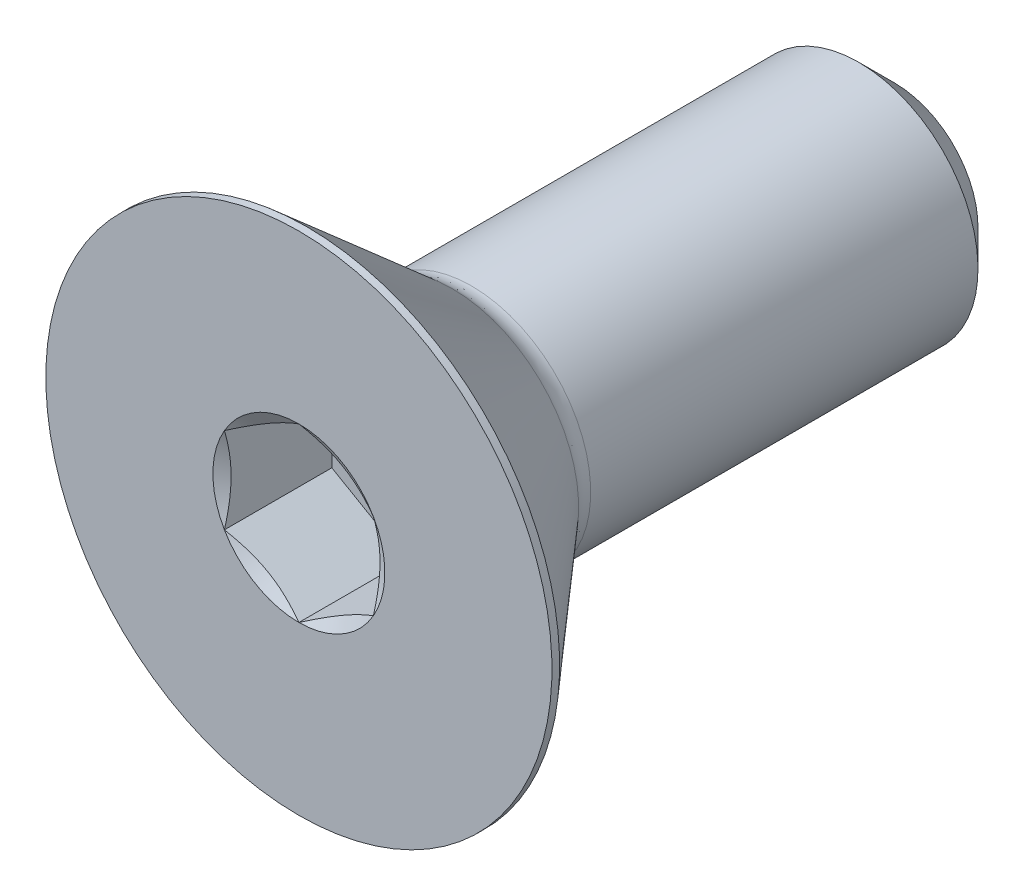
SolidWorks part; units mm, degrees
ref_plane "Front" through (0, 0, 0) normal (0, 0, 1) x (1, 0, 0)
ref_plane "Top" through (0, 0, 0) normal (0, 1, 0) x (1, 0, 0)
ref_plane "Right" through (0, 0, 0) normal (1, 0, 0) x (0, 0, -1)
sketch "Sketch1" plane through (0, 0, 0) normal (1, 0, 0) x (0, 0, -1)
  line L0 (0, 6.7437) -> (0.2045, 6.7437) construction
  line L1 (0.2045, 6.7437) -> (4.0894, 3.3666) construction
  line L2 (0, 3.175) -> (15.875, 3.175)
  line L3 (15.875, 3.175) -> (15.875, 0)
  line L4 (15.875, 0) -> (0, 0)
  line L5 (0, 0) -> (0, 6.7437) construction
  line L6 (0, 6.7437) -> (0, -6.7437) construction
  line L7 (15.875, 3.175) -> (15.875, -3.175) construction
  line L8 (0, -6.7437) -> (0.2045, -6.7437) construction
  line L9 (0.2045, -6.7437) -> (4.0894, -3.3666) construction
  line L11 (0, 3.175) -> (0, 0)
  line L12 (4.6018, 3.175) -> (4.6018, 0) construction
  line L13 (-9.525, 0) -> (-9.525, 3.175) construction
  arc A1 (4.0894, 3.3666) -> (4.6018, 3.175) centre (4.6018, 3.956) ccw construction
  dimension "D1" = 0.2045
  dimension "Head Ht" = 4.0894
  dimension "Head Dia" = 13.4874
  dimension "Dia" = 6.35
  dimension "Lg" = 15.875
  dimension "Head Angle" = 82
  dimension "Min Thread" = 25.4
revolve "Revolve1" add sketch "Sketch1" angle 360 mid plane about L4
sketch "Sketch3" plane through (0, 0, -15.875) normal (0, 0, -1) x (-1, 0, 0)
  circle A0 centre (0, 0) radius 3.175
curve "Helix/Spiral1" pitch 1.27 height 15.875 turns 12.5
sketch "Sketch2" plane through (0, 0, 0) normal (1, 0, 0) x (0, 0, -1)
  line L0 (15.875, 3.175) -> (16.9863, 3.175)
  line L1 (16.9863, 3.175) -> (16.51, 2.3501)
  line L2 (16.51, 2.3501) -> (16.3513, 2.3501)
  line L3 (16.3513, 2.3501) -> (15.875, 3.175)
  line L4 (16.1131, 2.7626) -> (16.7481, 2.7626) construction
  dimension "D1" = 60
  dimension "D2" = 0.1588
  dimension "D3" = 0.635
ref_plane "Plane2" through (0, 0, 9.525) normal (0, 0, 1) x (1, 0, 0)
chamfer "Chamfer1" distance 0.9525 angle 45 1 edges at (0, 3.175, -15.875)
sweep "Cut-Sweep1" [suppressed] cut profiles "Sketch2" path "Helix/Spiral1"
sketch "Sketch7" plane through (0, 0, 0) normal (1, 0, 0) x (0, 0, -1)
  line L0 (0, 6.7437) -> (0.2045, 6.7437) construction
  line L1 (0.2045, 6.7437) -> (4.0894, 3.3666) construction
  line L2 (0, 6.7437) -> (0.2045, 6.7437)
  line L3 (0.2045, 6.7437) -> (4.0894, 3.3666)
  line L4 (4.6018, 3.175) -> (4.6018, 0) construction
  line L5 (4.6018, 3.175) -> (4.6018, 0)
  line L7 (0, 0) -> (0, 6.7437) construction
  line L8 (0, 0) -> (0, 6.7437)
  line L9 (0, 0) -> (4.6018, 0)
  line L10 (7.4181, 0) -> (-7.4181, 0) construction
  arc A0 (4.0894, 3.3666) -> (4.6018, 3.175) centre (4.6018, 3.956) ccw construction
  arc A1 (4.0894, 3.3666) -> (4.6018, 3.175) centre (4.6018, 3.956) ccw
revolve "Revolve2" add sketch "Sketch7" angle 360 mid plane about L9
ref_plane "Plane1" through (0, 0, -4.6018) normal (0, 0, 1) x (1, 0, 0)
sketch "Sketch8" plane through (0, 0, -4.6018) normal (0, 0, 1) x (1, 0, 0)
  circle A0 centre (0, 0) radius 3.175
extrude "Boss-Extrude1" add sketch "Sketch8" against normal through all draft 46
sketch "Sketch5" plane through (0, 0, 0) normal (0, 0, 1) x (1, 0, 0)
  line L0 (0, 0) -> (-2.2914, 0) construction
  line L1 (0, 0) -> (-2.7496, 1.5875) construction
  line L2 (0, 0) -> (-2.7496, -1.5875) construction
  line L6 (0, 2.2914) -> (0, 1.8898) construction
  line L7 (0, 1.8898) -> (0, 1.4883) construction
  line L9 (0, 2.2914) -> (-1.9844, 1.1457)
  line L10 (-1.9844, 1.1457) -> (-1.9844, -1.1457)
  line L11 (-1.9844, -1.1457) -> (0, -2.2914)
  line L12 (0, -2.2914) -> (1.9844, -1.1457)
  line L13 (1.9844, -1.1457) -> (1.9844, 1.1457)
  line L14 (1.9844, 1.1457) -> (0, 2.2914)
  circle A0 centre (0, 0) radius 2.2914 construction
  circle A1 centre (0, 0) radius 1.8898 construction
  circle A2 centre (0, 0) radius 1.4883 construction
  circle A3 centre (0, 0) radius 1.9844 construction
  dimension "D3" = 2.9766
  dimension "Hex" = 3.9688
  dimension "D4" = 30
  dimension "D5" = 30
extrude "Cut-Extrude2" cut sketch "Sketch5" against normal blind 2.8626
sketch "Sketch6" plane through (0, 0, 0) normal (0, 0, 1) x (1, 0, 0)
  circle A0 centre (0, 0) radius 2.2914
extrude "Cut-Extrude3" cut sketch "Sketch6" against normal blind 2.8626 draft 60
sketch "Sketch9" [suppressed] plane through (0, 0, -3.6076) normal (0, 0, 1) x (1, 0, 0)
  circle A1 centre (0, 0) radius 2.413
  circle A2 centre (0, 0) radius 2.413
  point P0 (0, 2.413)
  dimension "D1" = 0
extrude "Boss-Extrude2" [suppressed] add sketch "Sketch9" against normal up to surface (15.4424 mm away)
sketch "Sketch10" plane through (0, 0, 0) normal (1, 0, 0) x (0, 0, -1)
  line L0 (15.875, 3.175) -> (15.875, -3.175) construction
  point P0 (13.97, -3.175)
  dimension "D1" = 1.905
equation "\"D3@Helix/Spiral1\" = \"Lg@Sketch1\""
equation "\"D2@Sketch2\" = \"D4@Helix/Spiral1\" * .125"
equation "\"D3@Sketch2\" = \"D4@Helix/Spiral1\" * .5"
equation "\"D1@Chamfer1\" = \"D4@Helix/Spiral1\" * .75"
equation "\"D1@Cut-Extrude2\" = \"Head Ht@Sketch1\" * .7"
equation "\"D1@Sketch1\" = \"Head Ht@Sketch1\" * .05"
equation "\"D1@Sketch10\" = \"D4@Helix/Spiral1\" * 1.5"
equation "\"D1@Cut-Extrude3\" = \"D1@Cut-Extrude2\""
equation "\"D3@Sketch5\" = \"Hex@Sketch5\" * .75"
